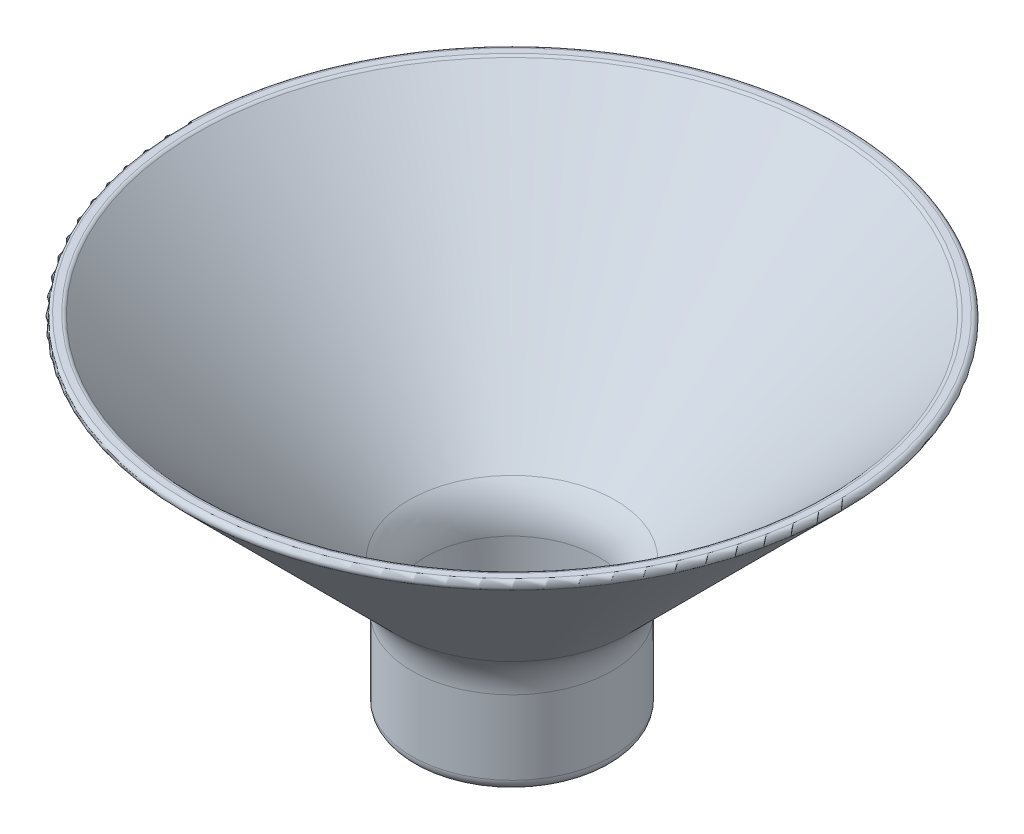
SolidWorks part; units mm, degrees
ref_plane "Front Plane" through (0, 0, 0) normal (0, 0, 1) x (1, 0, 0)
ref_plane "Top Plane" through (0, 0, 0) normal (0, 1, 0) x (1, 0, 0)
ref_plane "Right Plane" through (0, 0, 0) normal (1, 0, 0) x (0, 0, -1)
sketch "Sketch1" plane through (0, 0, 0) normal (0, 0, 1) x (1, 0, 0)
  line L0 (0, 0) -> (6, 0) construction
  line L1 (7.5, 2.5981) -> (7.5, 10)
  line L2 (7.5, 10) -> (27.5, 30)
  line L3 (0, 0) -> (0, 30) construction
  line L7 (27.5, 30) -> (29.1971, 30)
  line L9 (6, 0) -> (7.5, 2.5981)
  line L10 (8.7, 2.2765) -> (8.7, 9.5029)
  line L11 (8.7, 9.5029) -> (29.1971, 30)
  line L12 (8.7, 9.5029) -> (27.9971, 28.8) construction
  line L13 (6, 0) -> (8.7, 0)
  line L14 (7.0392, -0.6) -> (8.7, 2.2765) construction
  line L15 (27.9971, 28.8) -> (29.1971, 28.8) construction
  line L16 (8.7, 2.2765) -> (8.7, 0)
  dimension "D1" = 7.5
  dimension "D2" = 10
  dimension "D3" = 135
  dimension "D4" = 30
  dimension "D6" = 6
  dimension "D7" = 60
  dimension "D5" = 1.2
revolve "Revolve1" add sketch "Sketch1" angle 360 about L3
fillet "Fillet1" radius 5 2 edges at (0, 9.5029, -8.7) (0, 10, -7.5)
fillet "Fillet2" radius 0.4 2 edges at (0, 30, -27.5) (0, 30, -29.1971)
fillet "Fillet3" radius 1 1 edges at (0, 0, -8.7)
